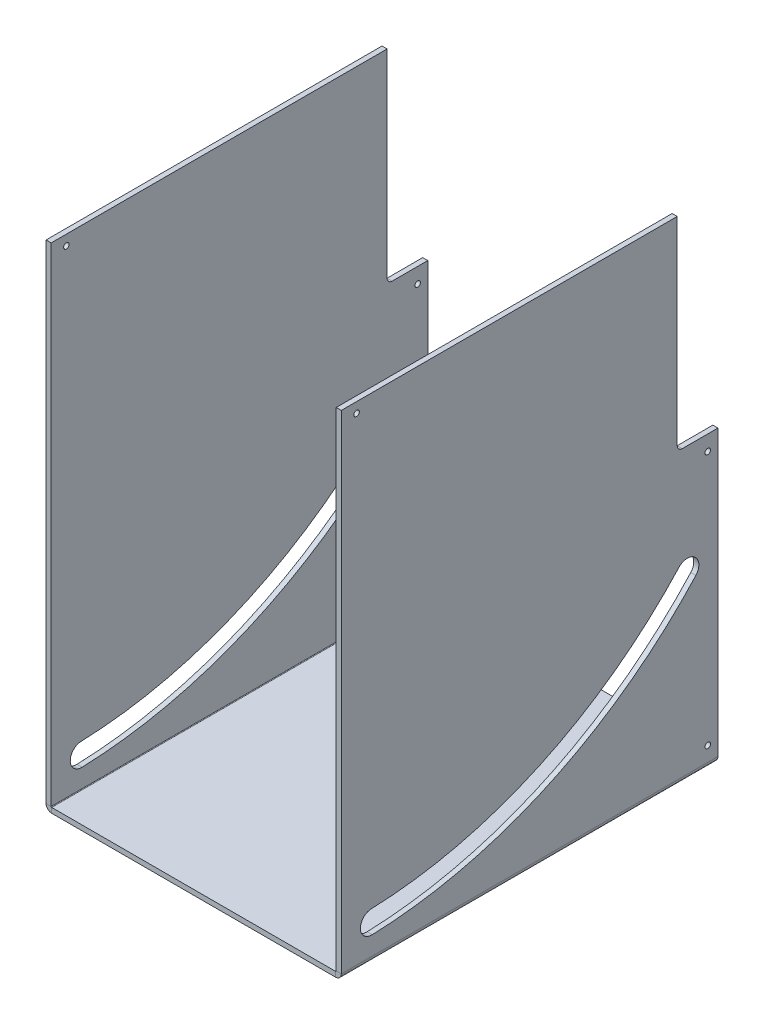
SolidWorks part; units mm, degrees
note: The reader was unsure of these and kept them because the rebuilt part matched: flange length of "Edge-Flange1", "Edge-Flange2".
material "PC High Viscosity"
ref_plane "Front Plane" through (0, 0, 0) normal (0, 0, 1) x (1, 0, 0)
ref_plane "Top Plane" through (0, 0, 0) normal (0, 1, 0) x (1, 0, 0)
ref_plane "Right Plane" through (0, 0, 0) normal (1, 0, 0) x (0, 0, -1)
sketch "Sketch1" plane through (0, 0, 0) normal (0, 1, 0) x (1, 0, 0)
  line L1 (0, 0) -> (368.3, 0)
  line L2 (0, 0) -> (0, 469.9)
  line L3 (0, 469.9) -> (368.3, 469.9)
  line L4 (368.3, 0) -> (368.3, 469.9)
  dimension "D1" = 368.3
  dimension "D2" = 469.9
base flange "Base-Flange1" sketch "Sketch1" thickness 6.35 reverse thickness direction yes parameters "D1"=0.7366
edge flange "Edge-Flange1" sketch "Sketch10" flange angle 90 flange length 615.95 flange position material inside bend radius 0.7366 thickness 6.35 relief rectangular parameters "D6"=10
sketch "Sketch10" plane through (368.3, 6.35, 0) normal (-1, 0, 0) x (0, 0, 1)
  line L1 (0, 0) -> (-469.9, 0) construction
  line L2 (-469.9, 0) -> (-469.9, 609.6)
  line L3 (-469.9, 609.6) -> (0, 609.6)
  line L4 (0, 609.6) -> (0, 0)
  line L5 (0, 0) -> (-469.9, 0)
bend "EdgeBend1" bend radius 0.7366 bend angle 90 parameters "D5"=1
edge flange "Edge-Flange2" sketch "Sketch13" flange angle 90 flange length 615.95 flange position material inside bend radius 0.7366 thickness 6.35 relief rectangular parameters "D6"=10
sketch "Sketch13" plane through (0, 6.35, 0) normal (1, 0, 0) x (0, 0, -1)
  line L1 (469.9, 0) -> (0, 0) construction
  line L2 (0, 0) -> (0, 609.6)
  line L3 (0, 609.6) -> (469.9, 609.6)
  line L4 (469.9, 609.6) -> (469.9, 0)
  line L5 (469.9, 0) -> (0, 0)
bend "EdgeBend2" bend radius 0.7366 bend angle 90 parameters "D5"=2
sketch "Sketch14" plane through (0, 0, 0) normal (-1, 0, 0) x (0, 0, 1)
  line L0 (0, 0) -> (-469.9, 0) construction
  line L1 (-469.9, 615.95) -> (-419.1, 615.95)
  line L2 (-469.9, 615.95) -> (-469.9, 361.95)
  line L3 (-469.9, 361.95) -> (-419.1, 361.95)
  line L4 (-419.1, 615.95) -> (-419.1, 361.95)
  line L5 (-469.9, 7.0866) -> (-469.9, 615.95) construction
  line L6 (0, 615.95) -> (0, 7.0866) construction
  circle A0 centre (-19.05, 603.25) radius 3.429
  circle A1 centre (-457.2, 342.9) radius 3.429
  circle A2 centre (-457.2, 25.4) radius 3.429
  dimension "D8" = 6.858
  dimension "D1" = 361.95
  dimension "D2" = 50.8
  dimension "D3" = 25.4
  dimension "D4" = 12.7
  dimension "D5" = 342.9
  dimension "D6" = 603.25
  dimension "D7" = 19.05
extrude "Cut-Extrude1" cut sketch "Sketch14" against normal through all normal cut yes
fillet "Fillet1" radius 6.35 2 edges at (3.175, 361.95, -419.1) (365.125, 361.95, -419.1)
sketch "Sketch15" plane through (0, 0, 0) normal (-1, 0, 0) x (0, 0, 1)
  line L0 (0, 615.95) -> (0, 7.0866) construction
  line L1 (0, 0) -> (-469.9, 0) construction
  arc A0 (-421.2529, 235.7172) -> (-37.6132, 58.7292) centre (-19.05, 603.25) ccw
  arc A1 (-442.3471, 216.4413) -> (-38.5868, 30.1708) centre (-19.05, 603.25) ccw
  arc A2 (-38.5868, 30.1708) -> (-37.6132, 58.7292) centre (-38.1, 44.45) ccw
  arc A3 (-421.2529, 235.7172) -> (-442.3471, 216.4413) centre (-431.8, 226.0792) ccw
  dimension "D1" = 38.1
  dimension "D5" = 14.2875
  dimension "D2" = 44.45
  dimension "D3" = 431.8
extrude "Cut-Extrude2" cut sketch "Sketch15" against normal through all normal cut yes
sketch "Bend-Lines1" [suppressed] plane through (0, 0, 0) normal (0, 1, 0) x (1, 0, 0)
sketch "Bounding-Box1" [suppressed] plane through (0, 0, 0) normal (0, 1, 0) x (1, 0, 0)
sheet metal parameters "Sheet-Metal1" thickness 6.35 parameters "D1"=0.7366
flat pattern "Flat-Pattern1" [suppressed]
sketch "Bend-Lines2" plane through (0, 0, 0) normal (0, 1, 0) x (1, 0, 0)
sketch3d "Bounding-Box2" [suppressed]
  line L0 (0, 0, 0) -> (0, 469.9, 0) construction
  line L1 (368.3, 0, 0) -> (368.3, 469.9, 0) construction
  line L2 (0, 0, 0) -> (368.3, 0, 0) construction
  line L3 (0, 469.9, 0) -> (368.3, 469.9, 0) construction
sheet metal parameters "Sheet-Metal2" thickness 6.35 parameters "D1"=0.7366
flat pattern "Flat-Pattern1"
sketch "Bend-Lines2" plane through (0, 0, 0) normal (0, -1, 0) x (-1, 0, 0)
  line L0 (-364.2856, 469.9) -> (-364.2856, 0) construction
  line L1 (-364.2856, 469.9) -> (-364.2856, 0) construction
sketch3d "Bounding-Box2" [suppressed]
  line L0 (-976.2211, 469.9, 0) -> (0, 469.9, 0) construction
  line L1 (-976.2211, 0, 0) -> (0, 0, 0) construction
  line L2 (-976.2211, 469.9, 0) -> (-976.2211, 0, 0) construction
  line L3 (0, 469.9, 0) -> (0, 0, 0) construction
bend of the flat pattern "Flatten-<EdgeBend1>1"
sheet metal parameters "Sheet-Metal3" thickness 6.35 parameters "D1"=0.7366
flat pattern "Flat-Pattern1"
sketch "Bend-Lines2" plane through (0, 0, 0) normal (0, -1, 0) x (-1, 0, 0)
  line L0 (-364.2856, 469.9) -> (-364.2856, 0) construction
  line L1 (-364.2856, 469.9) -> (-364.2856, 0) construction
  line L2 (-4.0144, 0) -> (-4.0144, 469.9) construction
  line L3 (-4.0144, 0) -> (-4.0144, 469.9) construction
sketch3d "Bounding-Box2" [suppressed]
  line L0 (-976.2211, 469.9, 0) -> (607.9211, 469.9, 0) construction
  line L1 (-976.2211, 0, 0) -> (607.9211, 0, 0) construction
  line L2 (-976.2211, 469.9, 0) -> (-976.2211, 0, 0) construction
  line L3 (607.9211, 469.9, 0) -> (607.9211, 0, 0) construction
bend of the flat pattern "Flatten-<EdgeBend1>1"
bend of the flat pattern "Flatten-<EdgeBend2>1"
sheet metal parameters "Sheet-Metal4" thickness 6.35 parameters "D1"=0.7366
flat pattern "Flat-Pattern1" [suppressed]
sketch "Bend-Lines2" plane through (0, 0, 0) normal (0, -1, 0) x (-1, 0, 0)
  line L0 (-364.2856, 469.9) -> (-364.2856, 0) construction
  line L1 (-364.2856, 469.9) -> (-364.2856, 0) construction
  line L2 (-4.0144, 0) -> (-4.0144, 469.9) construction
  line L3 (-4.0144, 0) -> (-4.0144, 469.9) construction
sketch3d "Bounding-Box2" [suppressed]
  line L0 (-976.2211, 469.9, 0) -> (607.9211, 469.9, 0) construction
  line L1 (-976.2211, 0, 0) -> (607.9211, 0, 0) construction
  line L2 (-976.2211, 469.9, 0) -> (-976.2211, 0, 0) construction
  line L3 (607.9211, 469.9, 0) -> (607.9211, 0, 0) construction
bend of the flat pattern "Flatten-<EdgeBend1>1"
bend of the flat pattern "Flatten-<EdgeBend2>1"
sketch "Sketch15-1" plane through (8.0289, 0, 0) normal (0, -1, 0) x (0, 0, 1)
  line L0 (0, 615.95) -> (0, -968.1923) construction
  line L1 (0, 0) -> (-469.9, 0) construction
  arc A0 (-421.2529, 235.7172) -> (-37.6132, 58.7292) centre (-19.05, 603.25) ccw
  arc A1 (-442.3471, 216.4413) -> (-38.5868, 30.1708) centre (-19.05, 603.25) ccw
  arc A2 (-38.5868, 30.1708) -> (-37.6132, 58.7292) centre (-38.1, 44.45) ccw
  arc A3 (-421.2529, 235.7172) -> (-442.3471, 216.4413) centre (-431.8, 226.0792) ccw
  dimension "D1" = 38.1
  dimension "D5" = 14.2875
  dimension "D2" = 44.45
  dimension "D3" = 431.8
sheet metal parameters "Sheet-Metal6" thickness 6.35 parameters "D1"=0.7366
flat pattern "Flat-Pattern1" [suppressed]
sketch "Bend-Lines2" plane through (0, 0, 0) normal (0, -1, 0) x (-1, 0, 0)
  line L0 (-364.2856, 469.9) -> (-364.2856, 0) construction
  line L1 (-364.2856, 469.9) -> (-364.2856, 0) construction
  line L2 (-4.0144, 0) -> (-4.0144, 469.9) construction
  line L3 (-4.0144, 0) -> (-4.0144, 469.9) construction
sketch3d "Bounding-Box2" [suppressed]
  line L0 (-976.2211, 469.9, 0) -> (607.9211, 469.9, 0) construction
  line L1 (-976.2211, 0, 0) -> (607.9211, 0, 0) construction
  line L2 (-976.2211, 469.9, 0) -> (-976.2211, 0, 0) construction
  line L3 (607.9211, 469.9, 0) -> (607.9211, 0, 0) construction
bend of the flat pattern "Flatten-<EdgeBend1>1"
bend of the flat pattern "Flatten-<EdgeBend2>1"
sketch "Sketch15-1" [suppressed] plane through (8.0289, 0, 0) normal (0, -1, 0) x (0, 0, 1)
  line L0 (0, 615.95) -> (0, -968.1923) construction
  line L1 (0, 0) -> (-469.9, 0) construction
  arc A0 (-421.2529, 235.7172) -> (-37.6132, 58.7292) centre (-19.05, 603.25) ccw
  arc A1 (-442.3471, 216.4413) -> (-38.5868, 30.1708) centre (-19.05, 603.25) ccw
  arc A2 (-38.5868, 30.1708) -> (-37.6132, 58.7292) centre (-38.1, 44.45) ccw
  arc A3 (-421.2529, 235.7172) -> (-442.3471, 216.4413) centre (-431.8, 226.0792) ccw
  dimension "D1" = 38.1
  dimension "D5" = 14.2875
  dimension "D2" = 44.45
  dimension "D3" = 431.8
